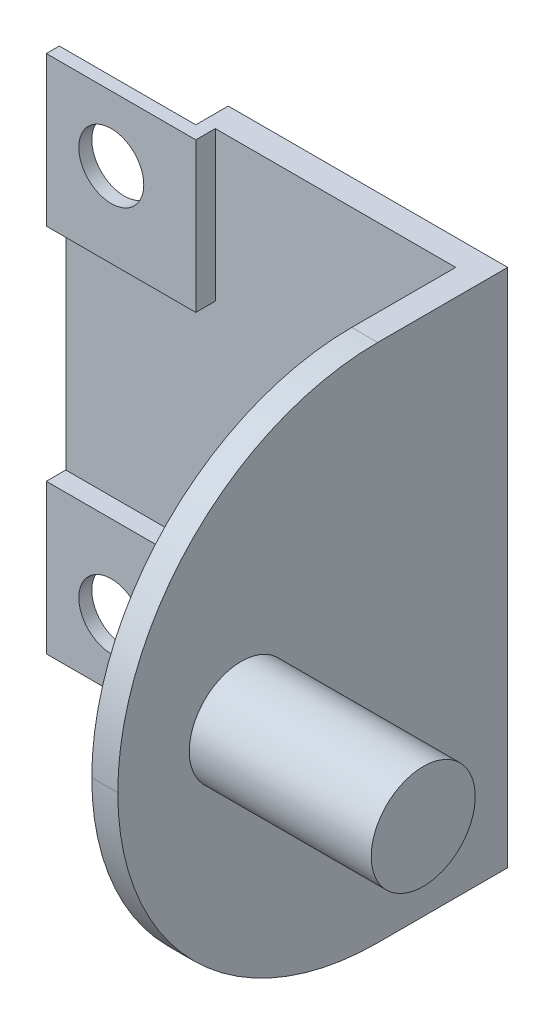
SolidWorks part; units mm, degrees
ref_plane "Plan de face" through (0, 0, 0) normal (0, 0, 1) x (1, 0, 0)
ref_plane "Plan de dessus" through (0, 0, 0) normal (0, 1, 0) x (1, 0, 0)
ref_plane "Plan de droite" through (0, 0, 0) normal (1, 0, 0) x (0, 0, -1)
sketch "Esquisse1" plane through (0, 0, 0) normal (0, 0, 1) x (1, 0, 0)
  line L1 (0, 0) -> (-32, 0)
  line L2 (0, 0) -> (0, 40)
  line L3 (0, 40) -> (-32, 40)
  line L4 (-32, 0) -> (-32, 40)
  dimension "D1" = 32
  dimension "D2" = 40
extrude "Boss.-Extru.1" add sketch "Esquisse1" along normal blind 2
sketch "Esquisse2" plane through (0, 0, 2) normal (0, 0, 1) x (1, 0, 0)
  line L0 (0, 40) -> (-32, 40) construction
  line L1 (0, 0) -> (-2, 0)
  line L2 (0, 0) -> (0, 40)
  line L3 (0, 40) -> (-2, 40)
  line L4 (-2, 0) -> (-2, 40)
  dimension "D1" = 2
extrude "Boss.-Extru.2" add sketch "Esquisse2" along normal blind 28
fillet "Congé1" radius 20 2 edges at (-1, 40, 30) (-1, 0, 30)
sketch "Esquisse3" plane through (0, 0, 0) normal (1, 0, 0) x (0, 0, -1)
  line L0 (0, 40) -> (0, 0) construction
  line L1 (-30, 20) -> (0, 20) construction
  circle A0 centre (-20.5, 20) radius 4
  dimension "D2" = 8
  dimension "D1" = 9.5
extrude "Enlèv. mat.-Extru.1" cut sketch "Esquisse3" against normal blind 30
sketch "Esquisse4" plane through (0, 0, 2) normal (0, 0, 1) x (1, 0, 0)
  line L0 (0, 20) -> (-32, 20) construction
  line L1 (-32, 40) -> (-21.5, 40)
  line L2 (-32, 40) -> (-32, 29.5)
  line L3 (-32, 29.5) -> (-21.5, 29.5)
  line L4 (-21.5, 40) -> (-21.5, 29.5)
  line L5 (-32, 40) -> (-32, 0) construction
  line L6 (-32, 10.5) -> (-21.5, 10.5)
  line L7 (-21.5, 0) -> (-21.5, 10.5)
  line L8 (-32, 0) -> (-21.5, 0)
  line L9 (-32, 0) -> (-32, 10.5)
  dimension "D1" = 10.5
  dimension "D2" = 10.5
extrude "Enlèv. mat.-Extru.2" cut sketch "Esquisse4" against normal blind 30
sketch "Esquisse5" plane through (0, 0, 2) normal (0, 0, 1) x (1, 0, 0)
  line L0 (0, 20) -> (-32, 20) construction
  line L1 (-21.5, 40) -> (-20.5, 40)
  line L2 (-21.5, 40) -> (-21.5, 28.5)
  line L3 (-21.5, 28.5) -> (-20.5, 28.5)
  line L4 (-20.5, 40) -> (-20.5, 28.5)
  line L5 (-32, 29.5) -> (-20.5, 29.5)
  line L6 (-32, 29.5) -> (-32, 28.5)
  line L7 (-32, 28.5) -> (-20.5, 28.5)
  line L8 (-20.5, 29.5) -> (-20.5, 28.5)
  line L9 (-32, 29.5) -> (-32, 10.5) construction
  line L10 (-21.5, 11.5) -> (-20.5, 11.5)
  line L11 (-20.5, 0) -> (-20.5, 11.5)
  line L12 (-21.5, 0) -> (-20.5, 0)
  line L13 (-21.5, 0) -> (-21.5, 11.5)
  line L14 (-32, 11.5) -> (-20.5, 11.5)
  line L15 (-20.5, 10.5) -> (-20.5, 11.5)
  line L16 (-32, 10.5) -> (-20.5, 10.5)
  line L17 (-32, 10.5) -> (-32, 11.5)
  line M7 (-21.5, 40) -> (-21.5, 29.5)
  line M8 (-21.5, 29.5) -> (-32, 29.5)
  line M9 (-32, 29.5) -> (-32, 10.5)
  line M10 (-32, 10.5) -> (-21.5, 10.5)
  line M11 (-21.5, 10.5) -> (-21.5, 0)
  line M12 (-21.5, 0) -> (-2, 0)
  line M14 (-2, 40) -> (-21.5, 40)
  dimension "D1" = 11.5
  dimension "D2" = 1
extrude "Boss.-Extru.5" add sketch "Esquisse5" along normal blind 1.5 contours L5 L2 L3 L4 | L7 L2 M9 M8 | L5 L4 M7 M14 | L13 L16 L11 L10 | L16 L11 M11 M12 | L14 L13 M9 M10 region at (-26.75, 11, 2) region at (-21, 34.75, 2) region at (-21, 29, 2) region at (-26.75, 29, 2) region at (-21, 11, 2) region at (-21, 5.25, 2)
sketch "Esquisse6" plane through (-21.5, 0, 0) normal (-1, 0, 0) x (0, 0, 1)
  line L0 (0, 29.5) -> (3.5, 29.5) construction
  line L1 (3.5, 40) -> (2.5, 40)
  line L2 (3.5, 40) -> (3.5, 29.5)
  line L3 (3.5, 29.5) -> (2.5, 29.5)
  line L4 (2.5, 40) -> (2.5, 29.5)
  line L5 (30, 20) -> (0, 20) construction
  line L6 (0, 29.5) -> (0, 10.5) construction
  line L7 (3.5, 10.5) -> (2.5, 10.5)
  line L8 (2.5, 0) -> (2.5, 10.5)
  line L9 (3.5, 0) -> (2.5, 0)
  line L10 (3.5, 0) -> (3.5, 10.5)
  dimension "D1" = 1
extrude "Boss.-Extru.6" add sketch "Esquisse6" along normal blind 10.5
sketch "Esquisse7" plane through (0, 0, 3.5) normal (0, 0, 1) x (1, 0, 0)
  line L0 (-32, 20) -> (0, 20) construction
  line L1 (-32, 28.5) -> (-32, 11.5) construction
  line L2 (-32, 40) -> (-22, 40) construction
  line L3 (-20.5, 40) -> (-32, 40) construction
  line L4 (-22, 40) -> (-22, 30) construction
  line L5 (-22, 30) -> (-32, 30) construction
  line L6 (-32, 40) -> (-32, 28.5) construction
  line L7 (-32, 30) -> (-32, 40) construction
  circle A0 centre (-27, 35) radius 2.5
  circle A1 centre (-27, 5) radius 2.5
  dimension "D5" = 5
  dimension "D1" = 10
  dimension "D2" = 10
  dimension "D3" = 5
  dimension "D4" = 5
extrude "Enlèv. mat.-Extru.3" cut sketch "Esquisse7" against normal blind 10.5
sketch "Esquisse8" plane through (-2, 0, 0) normal (-1, 0, 0) x (0, 0, 1)
  circle A0 centre (20.5, 20) radius 4
  dimension "D1" = 8
extrude "Boss.-Extru.7" add sketch "Esquisse8" against normal blind 16
